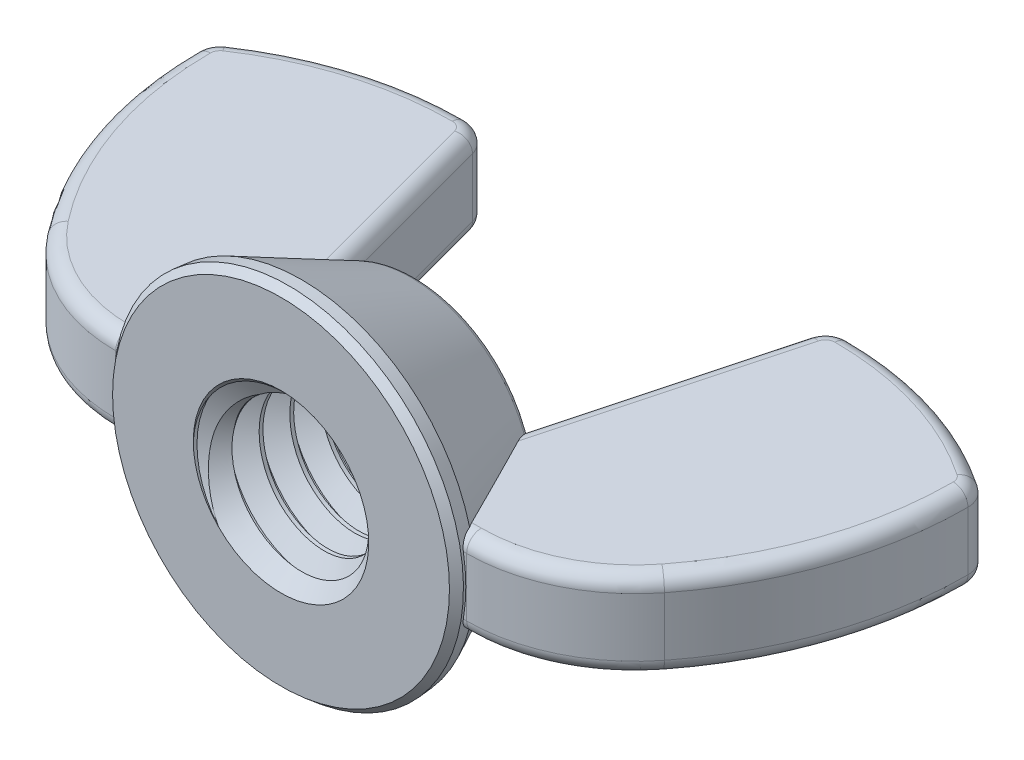
SolidWorks part; units mm, degrees
ref_plane "Front Plane" through (0, 0, 0) normal (0, 0, 1) x (1, 0, 0)
ref_plane "Top Plane" through (0, 0, 0) normal (0, 1, 0) x (1, 0, 0)
ref_plane "Right Plane" through (0, 0, 0) normal (1, 0, 0) x (0, 0, -1)
sketch "Sketch1" plane through (0, 0, 0) normal (0, 0, 1) x (1, 0, 0)
  circle A0 centre (0, 0) radius 2
  circle A1 centre (0, 0) radius 4
  dimension "D1" = 8
sketch "Sketch2" plane through (0, 0, 0) normal (0, 1, 0) x (1, 0, 0)
  line L0 (0, 0) -> (0, 8.6) construction
  line L1 (-2, 0) -> (2, 0) construction
  line L2 (-8.8, 8.6) -> (8.8, 8.6) construction
  line L3 (8.8, 8.6) -> (8.8, 0) construction
  line L4 (-8.8, 8.6) -> (-8.8, 0) construction
  line L5 (-8.8, 0) -> (8.8, 0) construction
  line L6 (-2.732, 3.096) -> (2.732, 3.096) construction
  line L7 (0, 0) -> (0, 3.096) construction
  line L8 (-4.3144, 0.4644) -> (4, 0.4644) construction
  line L9 (4, 0) -> (4, 3.096) construction
  line L10 (2.4588, 3.096) -> (3.9721, 8.7439)
  line L12 (2.732, 3.096) -> (2.732, 0.2322) construction
  line L13 (-4, 0) -> (4, 0) construction
  line L14 (4, 0.4644) -> (2.732, 3.096) construction
  line L15 (3.9721, 8.7439) -> (9.0361, 7.1957)
  line L16 (9.0361, 7.1957) -> (5.5412, 0.2322)
  line L17 (4, 0.2322) -> (5.5412, 0.2322)
  line L19 (2.4588, 0.2322) -> (4, 0.2322)
  line L20 (-2.4588, 3.096) -> (2.4588, 3.096) construction
  line L21 (2.4588, 3.096) -> (2.4588, 0.2322)
  circle A3 centre (8.2444, 6.8568) radius 0.5556 construction
  circle A4 centre (4.3599, 8.0444) radius 0.5556 construction
  dimension "D6" = 1.1111
  dimension "D2" = 3.096
  dimension "D4" = 5.4639
  dimension "D1" = 0.4644
  dimension "D3" = 25.727
  dimension "D5" = 0.2322
  dimension "D8" = 17
  dimension "D9" = 4.9175
  dimension "D7" = 15
sketch "Sketch13" plane through (0, 0, 0) normal (0, 1, 0) x (1, 0, 0)
  line L1 (2.4588, 3.096) -> (2.4588, 0.2322) construction
  line L2 (2.4588, 3.096) -> (3.9721, 8.7439) construction
  line L3 (-8.8, 8.6) -> (8.8, 8.6) construction
  line L4 (8.8, 8.6) -> (8.8, 0) construction
  line L5 (4, 0.2322) -> (5.5412, 0.2322) construction
  line L6 (2.4588, 0.2322) -> (4, 0.2322) construction
  line L7 (0, 0) -> (0, 3.096) construction
  line L8 (-2, 0) -> (2, 0) construction
  line L9 (0, 0) -> (0, 8.6) construction
  line L10 (-2.732, 3.096) -> (2.732, 3.096) construction
  line L11 (2.4588, 0.2322) -> (4, 0.2322)
  line L12 (2.4588, 3.096) -> (2.4588, 0.2322)
  line L13 (2.4588, 3.096) -> (3.8232, 8.1882)
  circle A0 centre (8.2444, 6.8568) radius 0.5556 construction
  circle A1 centre (4.3599, 8.0444) radius 0.5556 construction
  arc A5 (8.8, 6.8568) -> (8.5551, 7.3174) centre (8.2444, 6.8568) ccw
  arc A6 (4.3599, 8.6) -> (3.8232, 8.1882) centre (4.3599, 8.0444) ccw
  arc A7 (7.0284, 1.7097) -> (8.8, 6.8568) centre (0.4372, 6.8568) ccw
  arc A8 (8.5551, 7.3174) -> (4.3599, 8.6) centre (4.3599, 1.0977) ccw
  arc A10 (4, 0.2322) -> (7.0284, 1.7097) centre (4, 4.0746) ccw
extrude "Extrude2" add sketch "Sketch13" along normal mid plane 2
sketch "Sketch3" plane through (0, 0, 0) normal (0, 0, 1) x (1, 0, 0)
  circle A0 centre (0, 0) radius 4 construction
  circle A1 centre (0, 0) radius 4
extrude "Extrude1" add sketch "Sketch3" against normal up to vertex (0.4644 mm away) draft 5 separate body up to point (4, 0, -0.4644)
sketch "Sketch15" plane through (0, 0, -0.4644) normal (0, 0, -1) x (-1, 0, 0)
  circle A1 centre (0, 0) radius 3.9594
  circle A2 centre (0, 0) radius 3.9594
  dimension "D1" = 0
extrude "Extrude3" add sketch "Sketch15" along normal up to vertex (2.6316 mm away) draft 25.727 up to point (0, 0, -3.096)
fillet "Fillet3" radius 0.254 1 edges at (-2.6913, 0, -3.096)
sketch "Sketch12" plane through (0, 0, -3.096) normal (0, 0, -1) x (-1, 0, 0)
  circle A1 centre (0, 0) radius 3.9594
  circle A2 centre (0, 0) radius 3.9594 construction
  dimension "D1" = 7.9187
sketch "Sketch4" plane through (0, 0, 0) normal (0, 0, 1) x (1, 0, 0)
  circle A0 centre (0, 0) radius 2 construction
  circle A1 centre (0, 0) radius 2
extrude "Cut-Extrude1" cut sketch "Sketch4" against normal through all
sketch "Sketch5" plane through (0, 0, 0) normal (0, 0, 1) x (1, 0, 0)
  circle A0 centre (0, 0) radius 2 construction
  circle A1 centre (0, 0) radius 2
curve "Helix/Spiral1" pitch 0.7 height 5.096 radius 2 centre (0, 0, 0) axis (0, 0, -1) start towards (1, 0, 0) parameters "pitch"=0.7
sketch "Sketch6" plane through (0, 0, 0) normal (0, 1, 0) x (1, 0, 0)
  line L0 (-2, -0.6125) -> (-1.5453, -0.35)
  line L1 (-1.5453, -0.35) -> (-1.5453, -0.2625)
  line L2 (-1.5453, -0.2625) -> (-2, 0)
  line L3 (-2, -0.6125) -> (-2, 0)
  line L4 (-2, -0.3063) -> (-1.5453, -0.3063) construction
  line L5 (-1.7727, -0.4813) -> (-1.7727, -0.1313) construction
  line L6 (-2, 0) -> (2, 0) construction
  dimension "D1" = 60
  dimension "D2" = 0.0875
  dimension "D3" = 0.35
sweep "Sweep1" add profiles "Sketch6" path "Helix/Spiral1"
sketch "Sketch7" plane through (0, 0, 0) normal (0, 0, 1) x (1, 0, 0)
  circle A1 centre (0, 0) radius 4
  circle A2 centre (0, 0) radius 4
  dimension "D1" = 0
extrude "Cut-Extrude2" cut sketch "Sketch7" along normal through all
ref_plane "Plane1" through (0, 0, -3.096) normal (0, 0, 1) x (1, 0, 0)
sketch "Sketch8" plane through (0, 0, -3.096) normal (0, 0, 1) x (1, 0, 0)
  circle A0 centre (0, 0) radius 3.9594 construction
  circle A2 centre (0, 0) radius 3.9594
extrude "Cut-Extrude3" cut sketch "Sketch8" against normal through all
sketch "Sketch9" plane through (0, 0, 0) normal (0, 0, 1) x (1, 0, 0)
  circle A1 centre (0, 0) radius 2
  circle A2 centre (0, 0) radius 2
  dimension "D1" = 0
extrude "Cut-Extrude4" cut sketch "Sketch9" against normal through all draft 45
sketch "Sketch11" plane through (0, 0, -3.096) normal (0, 0, 1) x (1, 0, 0)
  circle A0 centre (0, 0) radius 2 construction
  circle A1 centre (0, 0) radius 1.9492
  circle A2 centre (0, 0) radius 2 construction
  dimension "D1" = 0.0508
extrude "Cut-Extrude5" cut sketch "Sketch11" along normal through all draft 45
chamfer "Chamfer1" distance 0.1741 angle 45 1 edges at (4, 0, 0) first distance on face at (-3.9594, 0, -0.4644)
fillet "Fillet4" radius 0.3333 14 edges at (3.2294, 1, -0.2322) (5.6848, 1, -0.6213) (4.0217, 1, -8.4852) (6.5533, 1, -8.2722) (8.735, 1, -7.1176) (3.2294, -1, -0.2322) (5.6848, -1, -0.6213) (4.0217, -1, -8.4852) (6.5533, -1, -8.2722) (8.735, -1, -7.1176) (8.3447, 1, -4.1351) (8.3447, -1, -4.1351) (3.141, 1, -5.6421) (3.141, -1, -5.6421)
mirror "Mirror6" about plane through (0, 0, 0) normal (1, 0, 0) of bodies 108 113
combine bodies "Combine2" operation type add bodies to combine 116 108 107
equation "\"D1@Sketch1\" = \"thread dia@Sketch1\"*1.725"
equation "\"D2@Sketch2\" = \"B@Sketch2\"*.36"
equation "\"D3@Helix/Spiral1\" = \"D2@Sketch2\"+2"
equation "\"D2@Sketch6\" = \"pitch@Helix/Spiral1\"*.125"
equation "\"D3@Sketch6\" = \"pitch@Helix/Spiral1\"*.5"
equation "\"D4@Sketch2\" = \"D1@Sketch12\"*.69"
equation "\"D1@Extrude2\" = \"D1@Sketch1\"*.25"
equation "\"D1@Sketch2\" = \"D2@Sketch2\"*.150"
equation "\"D5@Sketch2\" = \"D1@Sketch2\"/2"
equation "\"D3@Extrude3\" = \"D3@Sketch2\""
equation "\"D1@Chamfer1\" = \"D5@Sketch2\"*.75"
equation "\"D9@Sketch2\" = \"D4@Sketch2\"*.9"
equation "\"D6@Sketch2\" = \"D1@Extrude2\"/1.8"
equation "\"D1@Fillet4\" = \"D1@Extrude2\"/6"
